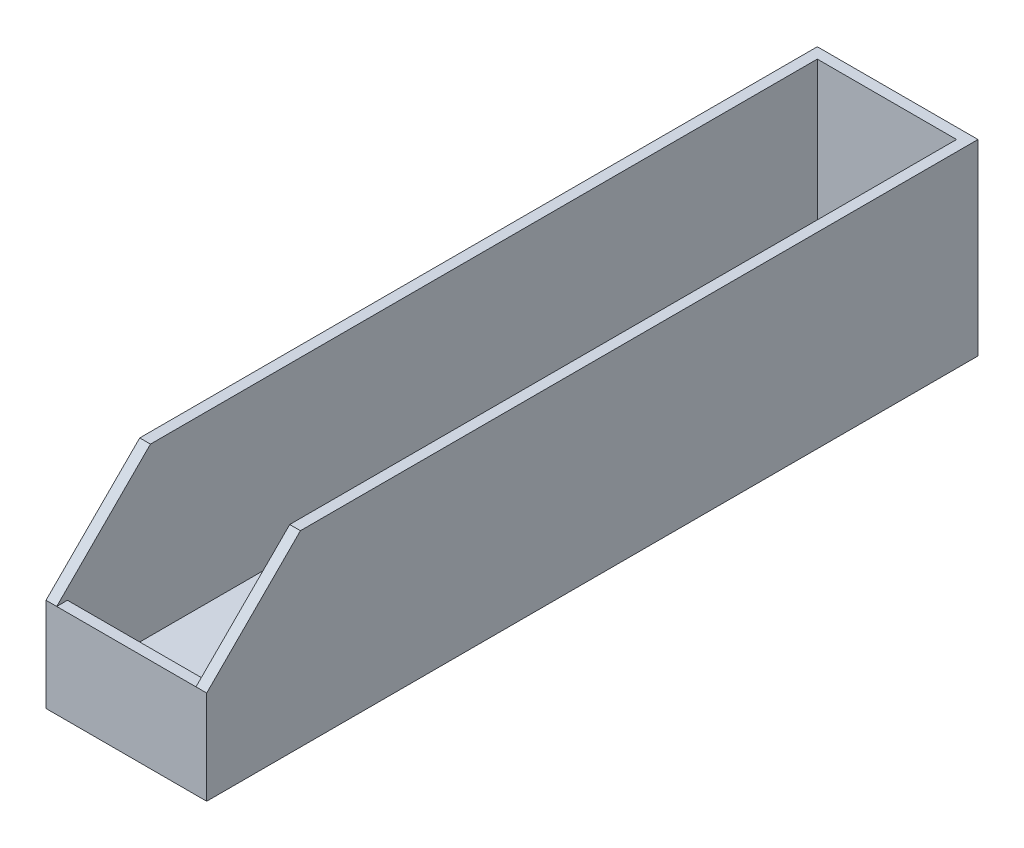
SolidWorks part; units mm, degrees
ref_plane "Front Plane" through (0, 0, 0) normal (0, 0, 1) x (1, 0, 0)
ref_plane "Top Plane" through (0, 0, 0) normal (0, 1, 0) x (1, 0, 0)
ref_plane "Right Plane" through (0, 0, 0) normal (1, 0, 0) x (0, 0, -1)
sketch "Sketch1" plane through (0, 0, 0) normal (0, 1, 0) x (1, 0, 0)
  line L0 (-13, -70) -> (-13, -72)
  line L1 (-15, 72) -> (15, 72)
  line L2 (-15, 72) -> (-15, -72)
  line L3 (-15, -72) -> (15, -72)
  line L4 (15, 72) -> (15, -72)
  line L5 (-15, 72) -> (15, -72) construction
  line L6 (-15, -72) -> (15, 72) construction
  line L7 (-13, 70) -> (13, 70)
  line L8 (-13, 70) -> (-13, -70)
  line L9 (-13, -70) -> (13, -70)
  line L10 (13, 70) -> (13, -70)
  line L11 (-13, 70) -> (13, -70) construction
  line L12 (-13, -70) -> (13, 70) construction
  line L13 (13, -70) -> (13, -72)
  point P0 (0, 0)
  point P6 (0, 0)
  dimension "D1" = 144
  dimension "D2" = 26
  dimension "D3" = 30
  dimension "D4" = 140
extrude "Boss-Extrude1" add sketch "Sketch1" along normal blind 4 contours L10 L7 L8 L9 region at (0, 0, 0)
extrude "Boss-Extrude2" add sketch "Sketch1<4>" along normal blind 35 contours L10 L13 L3 L4 L1 L2 L0 L8 L7 region at (-14.4709, 0, 71)
sketch "Sketch1<4>" plane through (0, 0, 0) normal (0, 1, 0) x (1, 0, 0) same geometry as "Sketch1"
extrude "Boss-Extrude3" add sketch "Sketch1<5>" along normal blind 17.5 contours L13 L9 L0 L3 region at (0, 0, 71)
sketch "Sketch1<5>" plane through (0, 0, 0) normal (0, 1, 0) x (1, 0, 0) same geometry as "Sketch1"
sketch "Sketch2" plane through (0, 4, 0) normal (0, 1, 0) x (1, 0, 0)
  line L0 (0, 30) -> (0, -30) construction
  circle A0 centre (0, 30) radius 2.5
  circle A1 centre (0, 30) radius 1.7
  circle A2 centre (0, -30) radius 2.5
  circle A3 centre (0, -30) radius 1.7
  point P6 (0, 0)
  dimension "D1" = 3.4
  dimension "D2" = 5
  dimension "D3" = 30
extrude "Cut-Extrude1" cut sketch "Sketch2" against normal up to next contours A1 | A3 region at (0, 4, -30) region at (0, 4, 30)
extrude "Cut-Extrude2" cut sketch "Sketch2<3>" against normal blind 2 contours A2 A3 | A1 A0 region at (-2.4293, 4, -30) region at (-2.4293, 4, 30)
sketch "Sketch2<3>" plane through (0, 4, 0) normal (0, 1, 0) x (1, 0, 0) same geometry as "Sketch2"
sketch "Sketch3" plane through (15, 0, 0) normal (1, 0, 0) x (0, 0, -1)
  line L0 (-72, 17.5) -> (-54.5, 35)
  line L1 (-72, 35) -> (-72, 0) construction
  line L2 (72, 35) -> (-72, 35) construction
  line L3 (-54.5, 35) -> (-72, 35)
  line L4 (-72, 35) -> (-72, 17.5)
extrude "Cut-Extrude3" cut sketch "Sketch3" against normal through all
